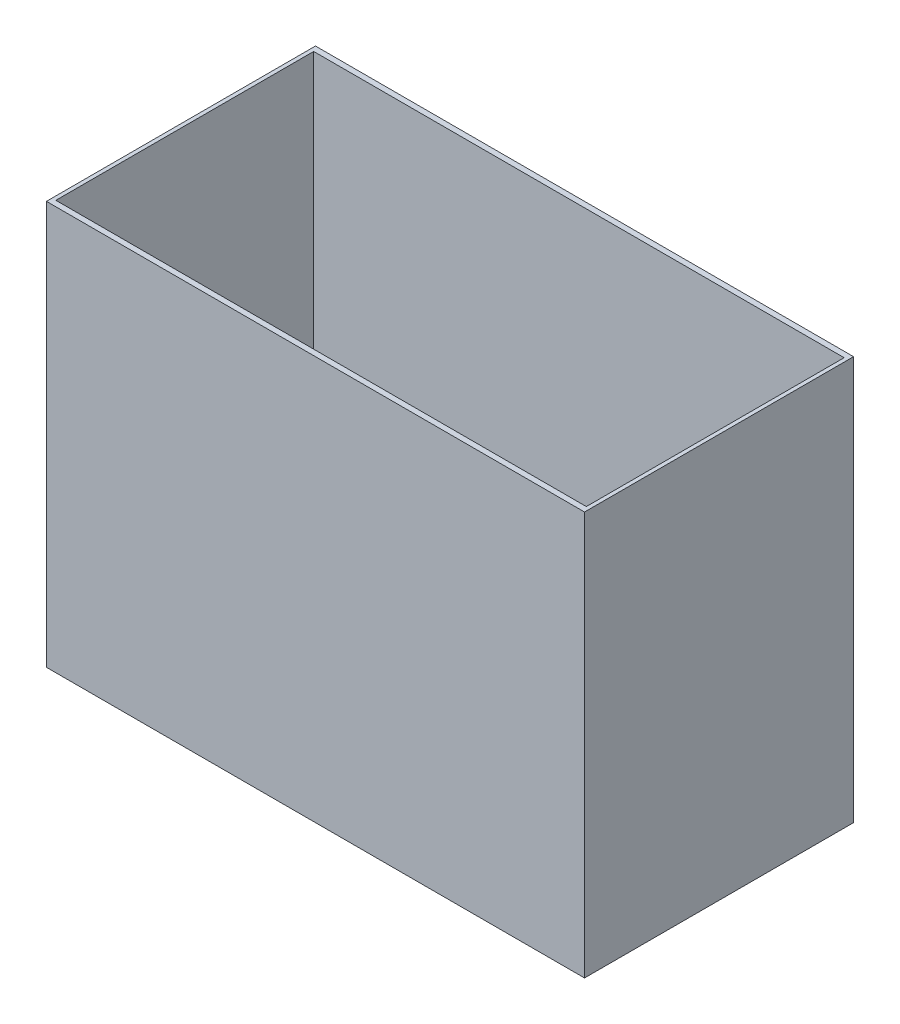
SolidWorks part; units mm, degrees
ref_plane "Front Plane" through (0, 0, 0) normal (0, 0, 1) x (1, 0, 0)
ref_plane "Top Plane" through (0, 0, 0) normal (0, 1, 0) x (1, 0, 0)
ref_plane "Right Plane" through (0, 0, 0) normal (1, 0, 0) x (0, 0, -1)
other "Bounding Box"
ref_plane "Default Plane" through (-292.1, 0, -139.7) normal (0, 1, 0) x (1, 0, 0)
sketch "Sketch1" plane through (0, 0, 0) normal (0, 1, 0) x (1, 0, 0)
  line L0 (-292.1, 0) -> (292.1, 0) construction
  line L1 (-292.1, 139.7) -> (292.1, 139.7)
  line L2 (-292.1, 139.7) -> (-292.1, -139.7)
  line L3 (-292.1, -139.7) -> (292.1, -139.7)
  line L4 (292.1, 139.7) -> (292.1, -139.7)
  line L5 (0, 139.7) -> (0, -139.7) construction
  point P8 (0, 0)
  dimension "D1" = 584.2
  dimension "D2" = 279.4
extrude "Boss-Extrude1" add sketch "Sketch1" along normal blind 12.7
sketch "Sketch2" plane through (0, 12.7, 0) normal (0, 1, 0) x (1, 0, 0)
  line L1 (-241.3, -95.25) -> (-152.4, -95.25)
  line L2 (-241.3, -95.25) -> (-241.3, -76.2)
  line L3 (-241.3, -76.2) -> (-152.4, -76.2)
  line L4 (-152.4, -95.25) -> (-152.4, -76.2)
  line L5 (-241.3, -95.25) -> (-152.4, -76.2) construction
  line L6 (-241.3, -76.2) -> (-152.4, -95.25) construction
  line L7 (-292.1, 139.7) -> (-292.1, -139.7) construction
  line L8 (-292.1, 0) -> (292.1, 0) construction
  line L9 (292.1, -139.7) -> (292.1, 139.7) construction
  line L10 (0, 0) -> (0, 121.6784) construction
  line L11 (241.3, -76.2) -> (152.4, -95.25) construction
  line L12 (241.3, -95.25) -> (152.4, -76.2) construction
  line L13 (152.4, -95.25) -> (152.4, -76.2)
  line L14 (241.3, -76.2) -> (152.4, -76.2)
  line L15 (241.3, -95.25) -> (241.3, -76.2)
  line L16 (241.3, -95.25) -> (152.4, -95.25)
  point P0 (-196.85, -85.725)
  point P17 (196.85, -85.725)
  dimension "D1" = 19.05
  dimension "D2" = 88.9
  dimension "D3" = 152.4
  dimension "D4" = 50.8
extrude "Boss-Extrude2" [suppressed] add sketch "Sketch2" along normal blind 304.8 separate body contours L2 L1 L4 L3
pattern_linear "LPattern1" [suppressed] count 2 spacing 304.8 of bodies 101
pattern_linear "LPattern2" [suppressed] count 2 spacing 215.9 of bodies 101
sketch "Sketch3" plane through (0, 0, 0) normal (0, 1, 0) x (1, 0, 0)
  line L1 (-304.8, -152.4) -> (304.8, -152.4)
  line L2 (-304.8, -152.4) -> (-304.8, 152.4)
  line L3 (-304.8, 152.4) -> (304.8, 152.4)
  line L4 (304.8, -152.4) -> (304.8, 152.4)
  line L5 (-304.8, -152.4) -> (304.8, 152.4) construction
  line L6 (-304.8, 152.4) -> (304.8, -152.4) construction
  line L7 (-300.482, -146.05) -> (300.482, -146.05)
  line L8 (-300.482, -146.05) -> (-300.482, 146.05)
  line L9 (-300.482, 146.05) -> (300.482, 146.05)
  line L10 (300.482, -146.05) -> (300.482, 146.05)
  line L11 (-300.482, -146.05) -> (300.482, 146.05) construction
  line L12 (-300.482, 146.05) -> (300.482, -146.05) construction
  point P0 (0, 0)
  point P6 (0, 0)
  dimension "D1" = 609.6
  dimension "D2" = 304.8
  dimension "D3" = 292.1
  dimension "D4" = 600.964
extrude "Boss-Extrude3" add sketch "Sketch3" along normal blind 457.2 separate body
